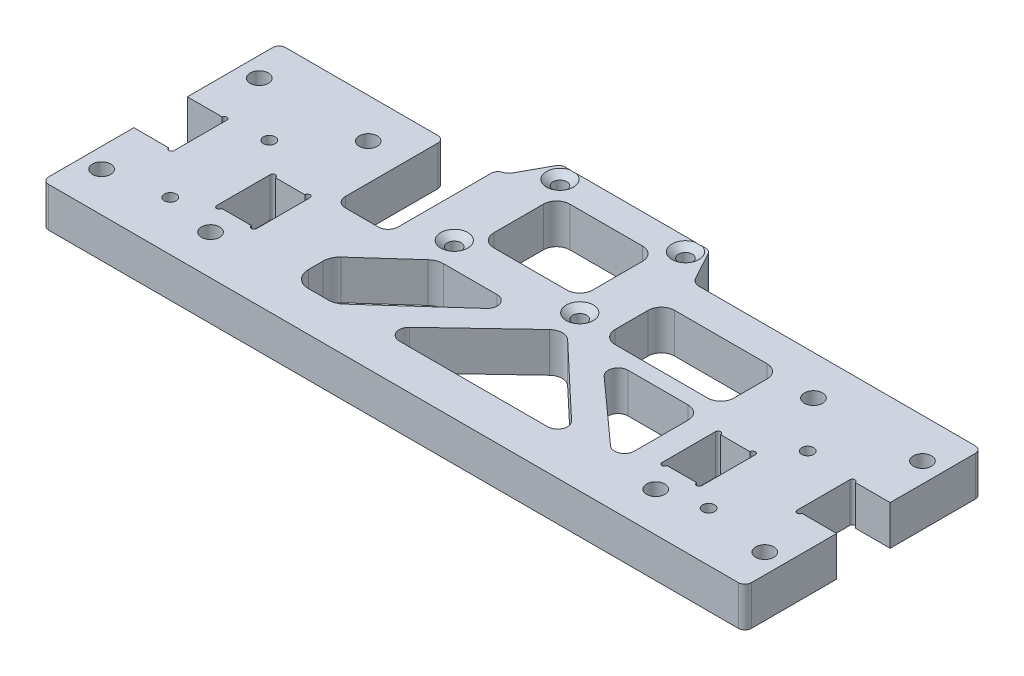
SolidWorks part; units mm, degrees
material "6061 Alloy"
ref_plane "Front Plane" through (0, 0, 0) normal (0, 0, 1) x (1, 0, 0)
ref_plane "Top Plane" through (0, 0, 0) normal (0, 1, 0) x (1, 0, 0)
ref_plane "Right Plane" through (0, 0, 0) normal (1, 0, 0) x (0, 0, -1)
sketch "Sketch1" plane through (0, 0, 0) normal (0, 1, 0) x (1, 0, 0)
  line L0 (106.4, 76.65) -> (106.4, 0) construction
  line L6 (32.95, 36.1) -> (32.95, 19.9)
  line L8 (45.05, 36.1) -> (45.05, 19.9)
  line L13 (0, 71.75) -> (68.4, 71.75)
  line L14 (68.4, 71.75) -> (74.4, 82.75)
  line L15 (74.4, 82.75) -> (119.4, 82.75)
  line L16 (119.4, 82.75) -> (125.4, 71.75)
  line L17 (125.4, 71.75) -> (212.8, 71.75)
  line L18 (32.95, 28) -> (45.05, 28) construction
  line L19 (34.55, 36.1) -> (43.45, 36.1)
  line L20 (34.55, 19.9) -> (43.45, 19.9)
  line L21 (179.85, 36.1) -> (179.85, 19.9)
  line L22 (178.25, 36.1) -> (169.35, 36.1)
  line L23 (167.75, 36.1) -> (167.75, 19.9)
  line L24 (178.25, 19.9) -> (169.35, 19.9)
  line L25 (12.1, 35.875) -> (0, 35.875) construction
  line L29 (12.1, 43.975) -> (12.1, 27.775)
  line L30 (10.5189, 43.975) -> (0, 43.975)
  line L31 (10.5189, 27.775) -> (0, 27.775)
  line L32 (0, 27.775) -> (0, 0)
  line L33 (0, 43.975) -> (0, 71.75)
  line L34 (200.7, 35.875) -> (212.8, 35.875) construction
  line L35 (212.8, 43.975) -> (212.8, 71.75)
  line L36 (212.8, 27.775) -> (212.8, 0)
  line L37 (202.2811, 27.775) -> (212.8, 27.775)
  line L38 (202.2811, 43.975) -> (212.8, 43.975)
  line L39 (200.7, 43.975) -> (200.7, 27.775)
  line L44 (106.4, 0) -> (212.8, 0)
  line L46 (106.4, 0) -> (0, 0)
  circle A0 centre (39, 59.75) radius 2.75
  circle A5 centre (39, 12) radius 2.75
  circle A6 centre (173.8, 59.75) radius 2.75
  circle A7 centre (173.8, 12) radius 2.75
  arc A8 (32.95, 36.1) -> (34.55, 36.1) centre (33.75, 36.1) cw
  arc A9 (45.05, 36.1) -> (43.45, 36.1) centre (44.25, 36.1) ccw
  arc A10 (32.95, 19.9) -> (34.55, 19.9) centre (33.75, 19.9) ccw
  arc A11 (45.05, 19.9) -> (43.45, 19.9) centre (44.25, 19.9) cw
  arc A12 (179.85, 19.9) -> (178.25, 19.9) centre (179.05, 19.9) cw
  arc A13 (179.85, 36.1) -> (178.25, 36.1) centre (179.05, 36.1) ccw
  arc A14 (167.75, 36.1) -> (169.35, 36.1) centre (168.55, 36.1) cw
  arc A15 (167.75, 19.9) -> (169.35, 19.9) centre (168.55, 19.9) ccw
  circle A16 centre (6, 12) radius 2.75
  circle A17 centre (6, 59.75) radius 2.75
  arc A18 (12.1, 27.775) -> (10.5189, 27.775) centre (11.3095, 27.8976) cw
  arc A19 (12.1, 43.975) -> (10.5189, 43.975) centre (11.3095, 43.8524) ccw
  arc A20 (200.7, 43.975) -> (202.2811, 43.975) centre (201.4905, 43.8524) cw
  arc A21 (200.7, 27.775) -> (202.2811, 27.775) centre (201.4905, 27.8976) ccw
  circle A22 centre (206.8, 59.75) radius 2.75
  circle A23 centre (206.8, 12) radius 2.75
  dimension "D12" = 5.5
  dimension "D16" = 5.5
  dimension "D17" = 0.8
  dimension "D18" = 0.8
  dimension "D19" = 0.8
  dimension "D20" = 0.8
  dimension "D21" = 5.5
  dimension "D22" = 5.5
  dimension "D27" = 0.8
  dimension "D1" = 212.8
  dimension "D2" = 71.75
  dimension "D5" = 61.35
  dimension "D6" = 12.1
  dimension "D4" = 11
  dimension "D7" = 6
  dimension "D8" = 38
  dimension "D10" = 45
  dimension "D11" = 16.2
  dimension "D14" = 6
  dimension "D13" = 12
  dimension "D25" = 16.2
  dimension "D3" = 12
  dimension "D23" = 16.2
  dimension "D26" = 12.1
  dimension "D9" = 6
  dimension "D15" = 6
  dimension "D24" = 33
  dimension "D28" = 33
  dimension "D29" = 0
  dimension "D30" = 0
  dimension "D31" = 0
extrude "Boss-Extrude1" add sketch "Sketch1" along normal blind 12
sketch "Sketch2" plane through (0, 12, 0) normal (0, 1, 0) x (1, 0, 0)
  line L1 (50.05, 85.2461) -> (66.05, 85.2461)
  line L2 (50.05, 85.2461) -> (50.05, 38.75)
  line L3 (50.05, 38.75) -> (66.05, 38.75)
  line L4 (66.05, 85.2461) -> (66.05, 38.75)
  line L5 (45.05, 19.9) -> (45.05, 36.1) construction
  line L12 (68.4, 71.75) -> (0, 71.75) construction
  dimension "D1" = 5
  dimension "D2" = 16
  dimension "D3" = 33
extrude "Cut-Extrude1" cut sketch "Sketch2" against normal through all
sketch "Sketch3" plane through (0, 12, 0) normal (0, 1, 0) x (1, 0, 0)
  line L1 (66.05, 38.75) -> (66.05, 71.75) construction
  line L2 (119.4, 82.75) -> (74.4, 82.75) construction
  circle A0 centre (78.05, 78.75) radius 2.1
  circle A1 centre (78.05, 46.75) radius 2.1
  circle A2 centre (116.05, 78.75) radius 2.1
  circle A3 centre (116.05, 46.75) radius 2.1
  dimension "D2" = 4.2
  dimension "D5" = 4.2
  dimension "D8" = 32
  dimension "D1" = 4
  dimension "D3" = 12
  dimension "D4" = 32
  dimension "D7" = 38
  dimension "D6" = 2
extrude "Cut-Extrude2" cut sketch "Sketch3" against normal through all
sketch "Sketch5" plane through (0, 12, 0) normal (0, 1, 0) x (1, 0, 0)
  line L3 (98.7821, 39) -> (82.5187, 39)
  line L11 (78.0261, 13.2835) -> (100.789, 33.7701)
  line L12 (66.05, 38.75) -> (66.05, 71.75) construction
  line L13 (115.8513, 37.7761) -> (94.0759, 17.1795)
  line L14 (118.6, 40.376) -> (118.6, 12) construction
  line L15 (96.1374, 12) -> (141.0626, 12)
  line L16 (121.3487, 37.7761) -> (143.1241, 17.1795)
  line L17 (138.4179, 39) -> (156.6, 39)
  line L18 (155.5931, 16.5062) -> (136.411, 33.7701)
  line L19 (160.6, 35) -> (160.6, 18.7361)
  line L20 (119.4, 82.75) -> (74.4, 82.75) construction
  line L21 (86.05, 73.75) -> (108.05, 73.75)
  line L22 (82.05, 69.75) -> (82.05, 54.75)
  line L23 (86.05, 50.75) -> (108.05, 50.75)
  line L24 (112.05, 69.75) -> (112.05, 54.75)
  line L25 (212.8, 71.75) -> (125.4, 71.75) construction
  line L26 (129.75, 61.75) -> (157.75, 61.75)
  line L27 (125.75, 57.75) -> (125.75, 47.75)
  line L28 (129.75, 43.75) -> (157.75, 43.75)
  line L29 (161.75, 57.75) -> (161.75, 47.75)
  line L30 (79.1739, 37.7165) -> (65.279, 25.2111)
  line L31 (167.75, 36.1) -> (167.75, 19.9) construction
  line L32 (63.6239, 21.4947) -> (63.6239, 17)
  line L33 (68.6239, 12) -> (74.6813, 12)
  arc A0 (121.3487, 37.7761) -> (115.8513, 37.7761) centre (118.6, 34.8701) ccw
  arc A1 (160.6, 35) -> (156.6, 39) centre (156.6, 35) ccw
  arc A3 (112.05, 69.75) -> (108.05, 73.75) centre (108.05, 69.75) ccw
  arc A4 (108.05, 50.75) -> (112.05, 54.75) centre (108.05, 54.75) ccw
  arc A5 (82.05, 54.75) -> (86.05, 50.75) centre (86.05, 54.75) ccw
  arc A6 (82.05, 69.75) -> (86.05, 73.75) centre (86.05, 69.75) cw
  arc A7 (155.5931, 16.5062) -> (160.6, 18.7361) centre (157.6, 18.7361) ccw
  arc A8 (136.411, 33.7701) -> (138.4179, 39) centre (138.4179, 36) cw
  arc A10 (141.0626, 12) -> (143.1241, 17.1795) centre (141.0626, 15) ccw
  arc A11 (96.1374, 12) -> (94.0759, 17.1795) centre (96.1374, 15) cw
  arc A12 (100.789, 33.7701) -> (98.7821, 39) centre (98.7821, 36) ccw
  arc A13 (161.75, 57.75) -> (157.75, 61.75) centre (157.75, 57.75) ccw
  arc A14 (157.75, 43.75) -> (161.75, 47.75) centre (157.75, 47.75) ccw
  arc A15 (125.75, 47.75) -> (129.75, 43.75) centre (129.75, 47.75) ccw
  arc A16 (125.75, 57.75) -> (129.75, 61.75) centre (129.75, 57.75) cw
  arc A17 (79.1739, 37.7165) -> (82.5187, 39) centre (82.5187, 34) cw
  arc A18 (63.6239, 21.4947) -> (65.279, 25.2111) centre (68.6239, 21.4947) cw
  arc A19 (68.6239, 12) -> (63.6239, 17) centre (68.6239, 17) cw
  arc A20 (74.6813, 12) -> (78.0261, 13.2835) centre (74.6813, 17) ccw
  point P25 (160.6, 39)
  point P33 (112.05, 50.75)
  point P36 (82.05, 50.75)
  point P39 (82.05, 73.75)
  point P42 (160.6, 12)
  point P45 (130.6, 39)
  point P48 (76.6, 12)
  point P51 (148.6, 12)
  point P54 (88.6, 12)
  point P57 (106.6, 39)
  point P68 (161.75, 61.75)
  point P71 (161.75, 43.75)
  point P76 (125.75, 61.75)
  dimension "D11" = 4
  dimension "D12" = 3
  dimension "D13" = 3
  dimension "D14" = 3
  dimension "D19" = 4
  dimension "D2" = 5
  dimension "D4" = 5
  dimension "D3" = 12
  dimension "D6" = 30
  dimension "D7" = 9
  dimension "D8" = 16
  dimension "D9" = 23
  dimension "D10" = 30
  dimension "D15" = 10
  dimension "D16" = 18
  dimension "D17" = 6
  dimension "D18" = 36
extrude "Cut-Extrude3" cut sketch "Sketch5" against normal through all
fillet "Fillet1" radius 3 4 edges at (68.4, 6, -71.75) (66.05, 6, -38.75) (50.05, 6, -38.75) (125.4, 6, -71.75)
fillet "Fillet2" radius 2 8 edges at (212.8, 6, -71.75) (119.4, 6, -82.75) (74.4, 6, -82.75) (50.05, 6, -71.75) (66.05, 6, -71.75) (0, 6, -71.75) (212.8, 6, 0) (0, 6, 0)
sketch "Sketch6" plane through (0, 12, 0) normal (0, 1, 0) x (1, 0, 0)
  line L0 (2, 0) -> (210.8, 0) construction
  line L1 (105.3, 92.584) -> (105.3, -38.973) construction
  line L2 (212.8, 2) -> (212.8, 27.775) construction
  circle A0 centre (186.8, 45) radius 1.8
  circle A1 centre (173.8, 59.75) radius 2.75 construction
  circle A2 centre (186.8, 15) radius 1.8
  circle A3 centre (23.8, 45) radius 1.8
  circle A4 centre (23.8, 15) radius 1.8
  circle A5 centre (173.8, 12) radius 2.75 construction
  dimension "D2" = 3.6
  dimension "D5" = 3.6
  dimension "D1" = 13
  dimension "D3" = 45
  dimension "D4" = 15
  dimension "D6" = 107.5
  dimension "D7" = 13
extrude "Cut-Extrude4" cut sketch "Sketch6" against normal through all
chamfer "Chamfer1" distance 2 angle 40 4 edges at (116.05, 12, -76.65) (116.05, 12, -44.65) (78.05, 12, -44.65) (78.05, 12, -76.65) first distance on face at (186.8, 12, -13.2)
equation "\"DriveMotorLength\"= 90mm"
equation "\"DriveMotorGap\"= 10mm"
equation "\"AluminumThickness\"= 0.5in"
equation "\"ChassisWidth\"= ( \"DriveMotorLength\" + \"AluminumThickness\" ) * 2 + \"DriveMotorGap\""
equation "\"RepeatMagnumHoleWidth\"= 19.05mm"
equation "\"MortiseWidth\"= 16mm"
equation "\"ChassisScrewThruHole\"= 5.5mm"
equation "\"D11@Sketch1\"=\"MortiseSlotWidth\""
equation "\"D12@Sketch1\"=\"ChassisScrewThruHole\""
equation "\"D16@Sketch1\"=\"ChassisScrewThruHole\""
equation "\"MortiseSlotWidth\"= 16.2mm"
equation "\"Dogbone\"= 0.8mm"
equation "\"D17@Sketch1\"=\"Dogbone\""
equation "\"D18@Sketch1\"=\"Dogbone\""
equation "\"D19@Sketch1\"=\"Dogbone\""
equation "\"D20@Sketch1\"=\"Dogbone\""
equation "\"D21@Sketch1\"=\"ChassisScrewThruHole\""
equation "\"D22@Sketch1\"=\"ChassisScrewThruHole\""
equation "\"D27@Sketch1\"=\"Dogbone\""
equation "\"D23@Sketch1\"=\"MortiseSlotWidth\""
equation "\"D25@Sketch1\"=\"MortiseSlotWidth\""
